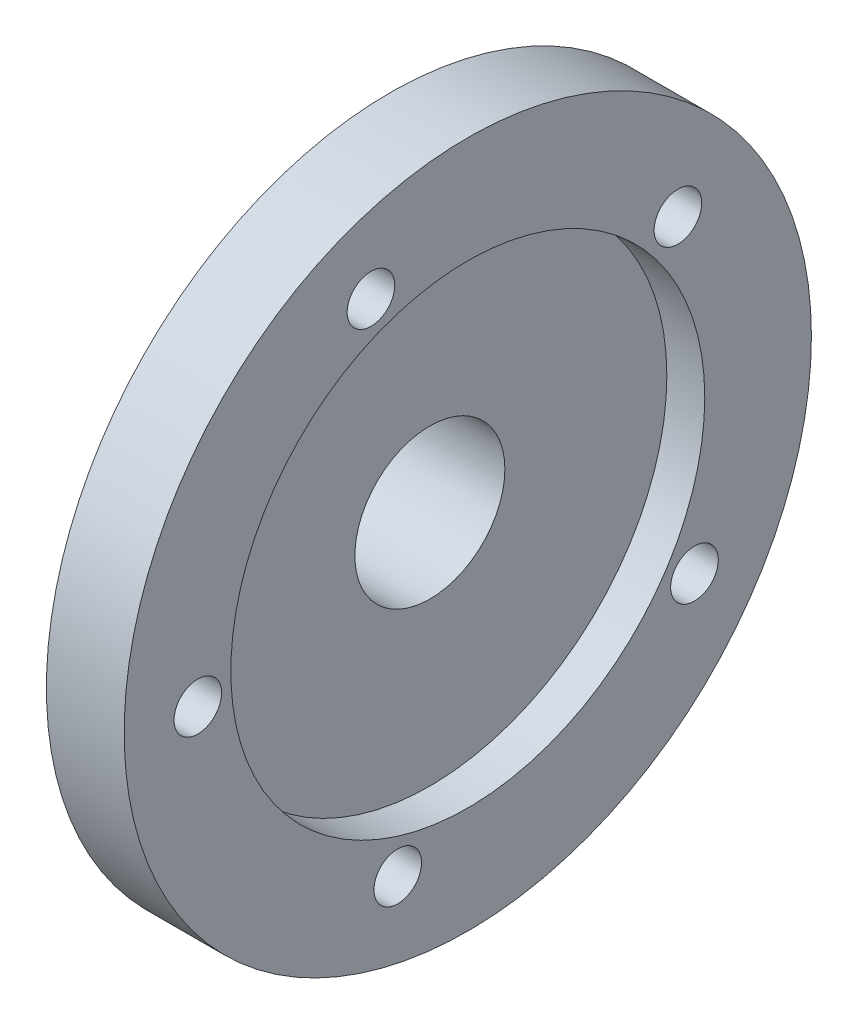
SolidWorks part; units mm, degrees
material "6061 Alloy"
ref_plane "Front Plane" through (0, 0, 0) normal (0, 0, 1) x (1, 0, 0)
ref_plane "Top Plane" through (0, 0, 0) normal (0, 1, 0) x (1, 0, 0)
ref_plane "Right Plane" through (0, 0, 0) normal (1, 0, 0) x (0, 0, -1)
sketch "Sketch1" plane through (0, 0, 0) normal (0, 0, 1) x (1, 0, 0)
  line L0 (0, 0) -> (-647.0721, 0) construction
  line L1 (-27.8573, 8.0391) -> (-14.0241, 8.0391)
  line L2 (-14.0241, 8.0391) -> (-14.0241, 25.4)
  line L3 (-14.0241, 25.4) -> (-9.9601, 25.4)
  line L5 (-18.2958, 17.8013) -> (-27.8573, 17.8013) construction
  line L6 (-27.8573, 17.8013) -> (-27.8573, 8.0391)
  line L7 (-9.9601, 25.4) -> (-9.9601, 36.83)
  line L8 (-9.9601, 36.83) -> (-18.2958, 36.83)
  line L10 (-12.8446, 3.3613) -> (-22.4061, 3.3613) construction
  line L11 (-4.5089, 4.8252) -> (-12.8446, 4.8252) construction
  line L12 (-18.2958, 36.83) -> (-27.8573, 17.8013)
  dimension "D1" = 16.0782
  dimension "D2" = 50.8
  dimension "D3" = 4.064
  dimension "D4" = 73.66
revolve "Revolve1" add sketch "Sketch1" angle 360 about L0
sketch "Sketch2" plane through (-9.9601, 0, 0) normal (1, 0, 0) x (0, 0, -1)
  circle A0 centre (-7.5051, -27.9836) radius 2.032 construction
  circle A1 centre (24.2948, -15.7852) radius 2.032 construction
  circle A2 centre (22.5201, 18.2278) radius 2.032 construction
  circle A3 centre (-10.3766, 27.0506) radius 2.032 construction
  circle A4 centre (-28.9332, -1.5096) radius 2.032 construction
  circle A5 centre (-7.5051, -27.9836) radius 2.032 construction
  circle A6 centre (24.2948, -15.7852) radius 2.032 construction
  circle A7 centre (22.5201, 18.2278) radius 2.032 construction
  circle A8 centre (-10.3766, 27.0506) radius 2.032 construction
  circle A9 centre (-28.9332, -1.5096) radius 2.032 construction
  circle A10 centre (-28.9332, -1.5096) radius 2.5527
  circle A11 centre (-10.3766, 27.0506) radius 2.5527
  circle A12 centre (24.2948, -15.7852) radius 2.5527
  circle A13 centre (-7.5051, -27.9836) radius 2.5527
  circle A14 centre (22.5201, 18.2278) radius 2.5527
  dimension "D1" = 5.1054
extrude "Cut-Extrude1" cut sketch "Sketch2" against normal through all
